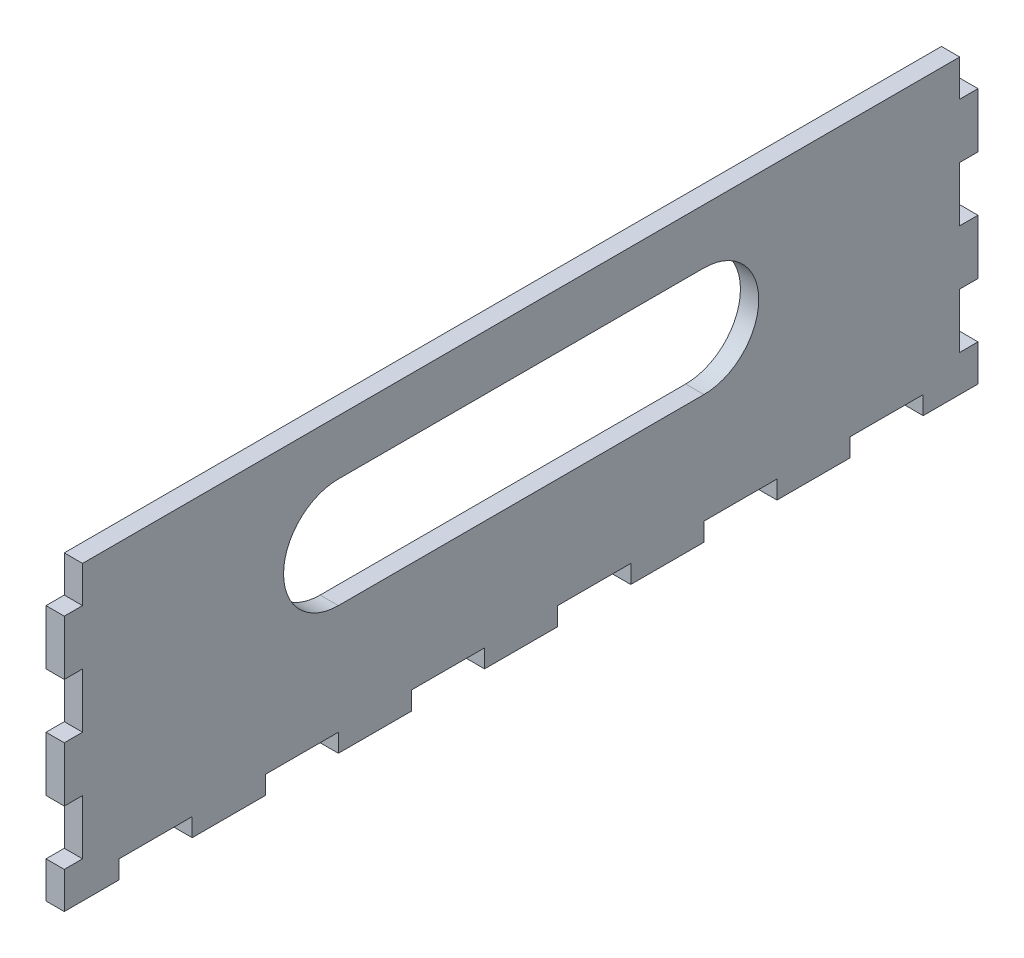
SolidWorks part; units mm, degrees
material "Oak"
ref_plane "Front Plane" through (0, 0, 0) normal (0, 0, 1) x (1, 0, 0)
ref_plane "Top Plane" through (0, 0, 0) normal (0, 1, 0) x (1, 0, 0)
ref_plane "Right Plane" through (0, 0, 0) normal (1, 0, 0) x (0, 0, -1)
sketch "Sketch2" plane through (0, 0, 0) normal (1, 0, 0) x (0, 0, -1)
  line L0 (-152.4, 101.6) -> (152.4, 101.6)
  line L1 (152.4, 101.6) -> (152.4, 88.9)
  line L2 (152.4, 88.9) -> (158.75, 88.9)
  line L3 (158.75, 88.9) -> (158.75, 69.85)
  line L4 (158.75, 69.85) -> (152.4, 69.85)
  line L5 (152.4, 69.85) -> (152.4, 50.8)
  line L6 (152.4, 50.8) -> (158.75, 50.8)
  line L7 (158.75, 50.8) -> (158.75, 31.75)
  line L8 (158.75, 0) -> (139.7, 0)
  line L9 (-158.75, 0) -> (-158.75, 12.7)
  line L10 (-158.75, 50.8) -> (-152.4, 50.8)
  line L11 (-152.4, 50.8) -> (-152.4, 69.85)
  line L12 (-152.4, 69.85) -> (-158.75, 69.85)
  line L13 (-158.75, 69.85) -> (-158.75, 88.9)
  line L14 (-158.75, 88.9) -> (-152.4, 88.9)
  line L15 (-152.4, 88.9) -> (-152.4, 101.6)
  line L16 (139.7, 0) -> (139.7, 6.35)
  line L21 (-63.5, 63.5) -> (63.5, 63.5) construction
  line L22 (-63.5, 82.55) -> (63.5, 82.55)
  line L23 (139.7, 6.35) -> (114.3, 6.35)
  line L24 (114.3, 6.35) -> (114.3, 0)
  line L25 (114.3, 0) -> (88.9, 0)
  line L26 (88.9, 0) -> (88.9, 6.35)
  line L27 (88.9, 6.35) -> (63.5, 6.35)
  line L28 (63.5, 6.35) -> (63.5, 0)
  line L29 (38.1, 0) -> (38.1, 6.35)
  line L30 (38.1, 6.35) -> (12.7, 6.35)
  line L31 (12.7, 6.35) -> (12.7, 0)
  line L32 (-12.7, 0) -> (-12.7, 6.35)
  line L33 (-12.7, 6.35) -> (-38.1, 6.35)
  line L34 (-38.1, 6.35) -> (-38.1, 0)
  line L35 (-63.5, 0) -> (-63.5, 6.35)
  line L36 (-63.5, 6.35) -> (-88.9, 6.35)
  line L37 (-88.9, 6.35) -> (-88.9, 0)
  line L38 (-114.3, 0) -> (-114.3, 6.35)
  line L39 (-114.3, 6.35) -> (-139.7, 6.35)
  line L40 (-139.7, 6.35) -> (-139.7, 0)
  line L41 (63.5, 0) -> (38.1, 0)
  line L42 (12.7, 0) -> (-12.7, 0)
  line L43 (-38.1, 0) -> (-63.5, 0)
  line L44 (-88.9, 0) -> (-114.3, 0)
  line L45 (-139.7, 0) -> (-158.75, 0)
  line L46 (-158.75, 31.75) -> (-152.4, 31.75)
  line L47 (-152.4, 31.75) -> (-152.4, 12.7)
  line L48 (-152.4, 12.7) -> (-158.75, 12.7)
  line L49 (-158.75, 31.75) -> (-158.75, 50.8)
  line L50 (0, 55) -> (0, -55) construction
  line L51 (152.4, 12.7) -> (158.75, 12.7)
  line L52 (152.4, 31.75) -> (152.4, 12.7)
  line L53 (158.75, 31.75) -> (152.4, 31.75)
  line L54 (158.75, 12.7) -> (158.75, 0)
  line L55 (-63.5, 44.45) -> (63.5, 44.45)
  arc A4 (-63.5, 82.55) -> (-63.5, 44.45) centre (-63.5, 63.5) ccw
  arc A5 (63.5, 44.45) -> (63.5, 82.55) centre (63.5, 63.5) ccw
  point P2 (0, 63.5)
  point P20 (0, 63.5)
  point P59 (0, 0)
  point P60 (0, 0)
  dimension "D7" = 19.05
  dimension "D1" = 304.8
  dimension "D2" = 6.35
  dimension "D3" = 12.7
  dimension "D4" = 101.6
  dimension "D5" = 19.05
  dimension "D6" = 19.05
  dimension "D8" = 158.75
  dimension "D9" = 127
  dimension "D10" = 0
  dimension "D11" = 19.05
  dimension "D16" = 25.4
  dimension "D17" = 6.35
  dimension "D18" = 19.05
  dimension "D20" = 25.4
  dimension "D21" = 6.35
  dimension "D22" = 19.05
  dimension "D23" = 19.05
  dimension "D19" = 6
extrude "Boss-Extrude1" add sketch "Sketch2" along normal blind 6.35
